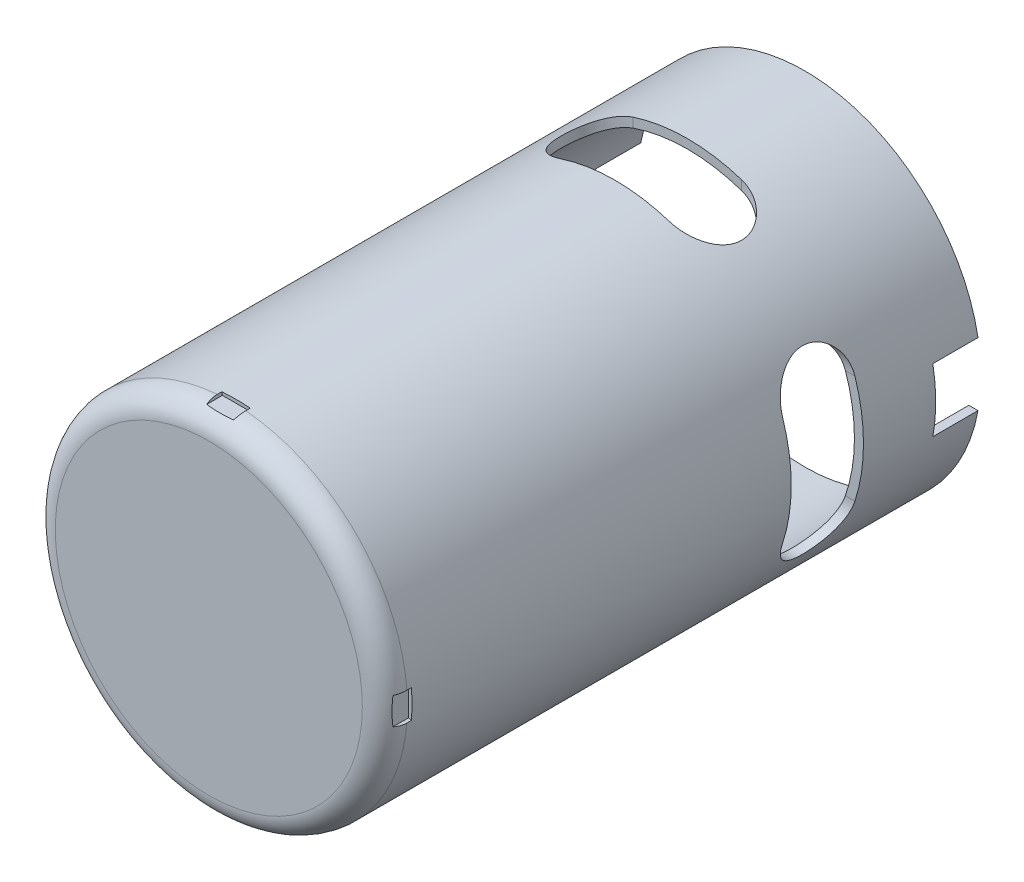
SolidWorks part; units mm, degrees
ref_plane "Front Plane" through (0, 0, 0) normal (0, 0, 1) x (1, 0, 0)
ref_plane "Top Plane" through (0, 0, 0) normal (0, 1, 0) x (1, 0, 0)
ref_plane "Right Plane" through (0, 0, 0) normal (1, 0, 0) x (0, 0, -1)
sketch "Sketch1" plane through (0, 0, 0) normal (0, 0, 1) x (1, 0, 0)
  circle A0 centre (0, 0) radius 19.5
  dimension "D1" = 39
extrude "Boss-Extrude1" add sketch "Sketch1" along normal blind 66
fillet "Fillet1" radius 2.5 1 edges at (19.5, 0, 66)
sketch "Sketch2" plane through (0, 0, 66) normal (0, 0, 1) x (1, 0, 0)
  line L0 (0, 0) -> (0, 19.1189) construction
  line L1 (-1.5, 19.1189) -> (1.5, 19.1189)
  line L2 (-1.5585, 19.4376) -> (-1.5, 19.1189)
  line L3 (1.5832, 19.4356) -> (1.5, 19.1189)
  line L4 (19.1189, 1.5) -> (19.1189, -1.5)
  line L5 (19.4376, 1.5585) -> (19.1189, 1.5)
  line L6 (19.4356, -1.5832) -> (19.1189, -1.5)
  line L7 (1.5, -19.1189) -> (-1.5, -19.1189)
  line L8 (1.5585, -19.4376) -> (1.5, -19.1189)
  line L9 (-1.5832, -19.4356) -> (-1.5, -19.1189)
  line L10 (-19.1189, -1.5) -> (-19.1189, 1.5)
  line L11 (-19.4376, -1.5585) -> (-19.1189, -1.5)
  line L12 (-19.4356, 1.5832) -> (-19.1189, 1.5)
  arc A1 (-1.5585, 19.4376) -> (1.5832, 19.4356) centre (0, 0) cw
  circle A2 centre (0, 0) radius 19.5 construction
  arc A3 (19.4376, 1.5585) -> (19.4356, -1.5832) centre (0, 0) cw
  arc A4 (1.5585, -19.4376) -> (-1.5832, -19.4356) centre (0, 0) cw
  arc A5 (-19.4376, -1.5585) -> (-19.4356, 1.5832) centre (0, 0) cw
  dimension "D1" = 3
  dimension "D2" = 4
extrude "Cut-Extrude1" cut sketch "Sketch2" against normal blind 3
sketch "Sketch3" plane through (0, 0, 0) normal (1, 0, 0) x (0, 0, -1)
  line L0 (0, -19.5) -> (0, 19.5) construction
  line L1 (0, -3.5) -> (-5, -3.5)
  line L2 (0, -3.5) -> (0, 3.5)
  line L3 (0, 3.5) -> (-5, 3.5)
  line L4 (-5, -3.5) -> (-5, 3.5)
  dimension "D1" = 7
  dimension "D2" = 5
shell "Shell2" thickness 1 removed face at (19.5, 0, 0)
extrude "Cut-Extrude3" cut sketch "Sketch3" against normal blind 35 and the other way blind 58
sketch "Sketch4" plane through (0, 0, 0) normal (0, 1, 0) x (1, 0, 0)
  line L0 (0, 0) -> (0, -13) construction
  line L1 (-6, -17) -> (6, -17) construction
  line L2 (-6, -13) -> (6, -13)
  line L3 (-6, -21) -> (6, -21)
  arc A0 (-6, -13) -> (-6, -21) centre (-6, -17) ccw
  arc A1 (6, -21) -> (6, -13) centre (6, -17) ccw
  point P5 (0, -17)
  dimension "D2" = 4
  dimension "D1" = 13
  dimension "D3" = 12
extrude "Cut-Extrude4" cut sketch "Sketch4" against normal through all and the other way blind 38
pattern_circular "CirPattern1" count 4 over 360 about axis through (0, 0, 66) along (0, 0, 1) of "Cut-Extrude4"
